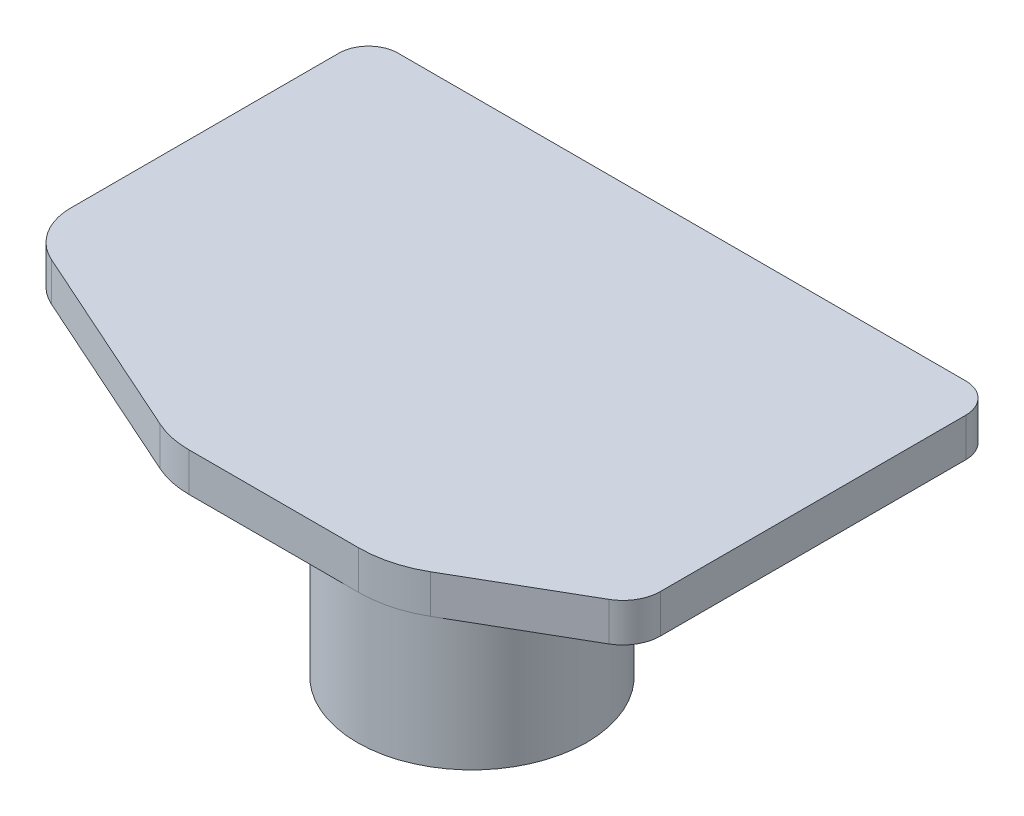
SolidWorks part; units mm, degrees
ref_plane "Front Plane" through (0, 0, 0) normal (0, 0, 1) x (1, 0, 0)
ref_plane "Top Plane" through (0, 0, 0) normal (0, 1, 0) x (1, 0, 0)
ref_plane "Right Plane" through (0, 0, 0) normal (1, 0, 0) x (0, 0, -1)
sketch "Sketch1" plane through (0, 0, 0) normal (0, 1, 0) x (1, 0, 0)
  line L0 (132.1174, -48.5134) -> (94.0174, -70.5105)
  line L1 (-62.5326, 75.1851) -> (128.4674, 75.1851)
  line L2 (-72.5326, 65.1851) -> (-72.5326, -25.0665)
  line L3 (17.8174, -75.6149) -> (74.9674, -75.6149)
  line L4 (138.4674, 65.1851) -> (138.4674, -37.5149)
  line L5 (-72.5326, 75.1851) -> (104.2074, -64.6273) construction
  line L6 (-25.8985, -58.9082) -> (138.4674, 75.1851) construction
  line L7 (-60.707, -43.3197) -> (5.5557, -72.9946)
  line L8 (17.8174, -75.6149) -> (-72.5326, -75.6149) construction
  line L9 (-72.5326, -75.6149) -> (-72.5326, -25.0665) construction
  line L10 (74.9674, -75.6149) -> (138.4674, -75.6149) construction
  line L11 (138.4674, -75.6149) -> (138.4674, -37.5149) construction
  line L12 (74.9674, -37.5149) -> (138.4674, -37.5149) construction
  line L13 (113.0674, -37.5149) -> (113.0674, -6.4349) construction
  arc A0 (132.1174, -48.5134) -> (138.4674, -37.5149) centre (125.7674, -37.5149) ccw
  arc A1 (74.9674, -75.6149) -> (94.0174, -70.5105) centre (74.9674, -37.5149) ccw
  arc A2 (17.8174, -75.6149) -> (5.5557, -72.9946) centre (17.8174, -45.6149) cw
  arc A3 (-60.707, -43.3197) -> (-72.5326, -25.0665) centre (-52.5326, -25.0665) cw
  arc A4 (-72.5326, 65.1851) -> (-62.5326, 75.1851) centre (-62.5326, 65.1851) cw
  arc A5 (138.4674, 65.1851) -> (128.4674, 75.1851) centre (128.4674, 65.1851) ccw
  arc A6 (94.0174, -70.5105) -> (74.9674, -75.6149) centre (74.9674, -37.5149) ccw construction
  point P0 (0, -38)
  dimension "D2" = 38.1
  dimension "D4" = 30
  dimension "D5" = 20
  dimension "D6" = 10
  dimension "D7" = 10
  dimension "D11" = 25.4
  dimension "D3" = 211
  dimension "D8" = 150.8
  dimension "D9" = 30
  dimension "D10" = 57.15
sketch "Sketch3" plane through (0, 0, 0) normal (0, 1, 0) x (1, 0, 0)
  line L2 (17.8174, -75.6149) -> (74.9674, -75.6149) construction
  line L3 (138.4674, 65.1851) -> (138.4674, -37.5149) construction
  circle A0 centre (74.4674, -37) radius 38.6149
  dimension "D1" = 64
extrude "Boss-Extrude2" add sketch "Sketch1" along normal blind 13
extrude "Boss-Extrude3" add sketch "Sketch3" against normal blind 44
ref_point "Point2"
ref_point "Point3"
ref_axis "Axis1" through (74.4674, 0, 37) along (0, -1, 0)
ref_axis "Axis2" through (-26.438, 13, 140.0554) along (0.866, 0, -0.5)
ref_plane "Plane1" through (39.8291, 0, -22.9953) normal (0.866, 0, -0.5) x (-0.25, -0.866, -0.433)
ref_axis "Axis3" through (70.6923, 13, 30.4613) along (0.5, 0, 0.866)
ref_plane "Plane2" through (34.6383, 0, 59.9953) normal (0.5, 0, 0.866) x (0.866, 0, -0.5)
ref_axis "Axis4" through (74.4674, -44, 37) along (0.5, 0, 0.866)
